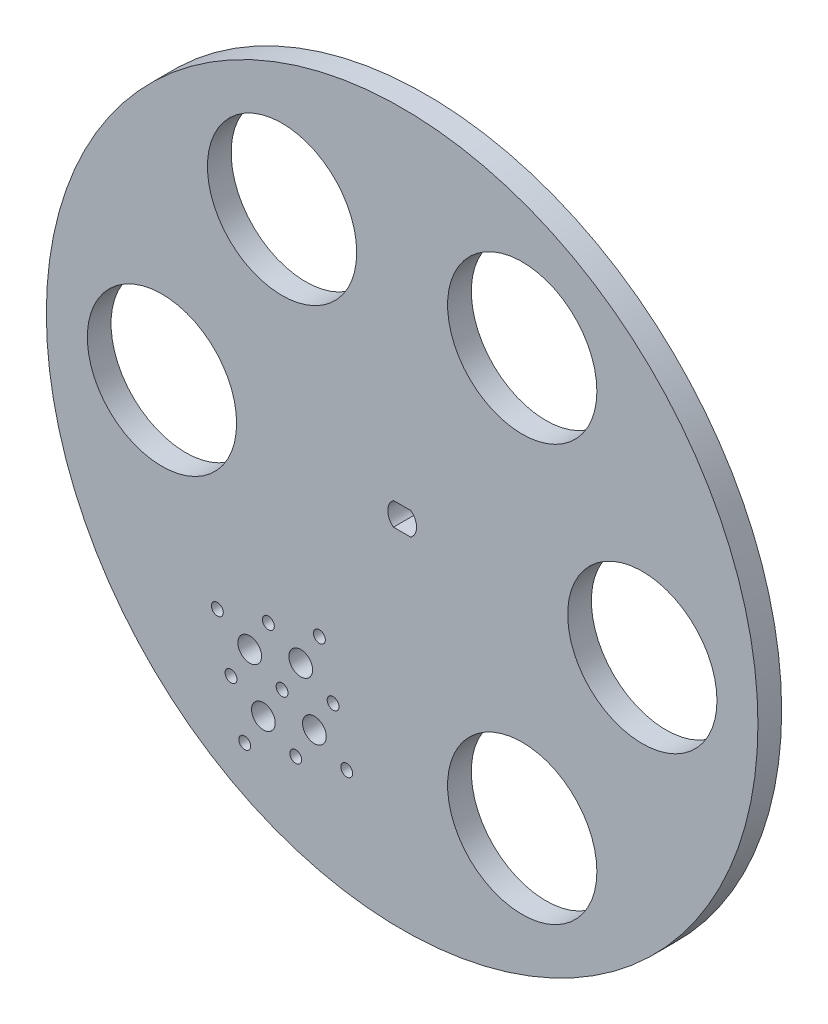
SolidWorks part; units mm, degrees
note: The reader was unsure of these and kept them because the rebuilt part matched: shared geometry of "草圖2<4>".
ref_plane "前基準面" through (0, 0, 0) normal (0, 0, 1) x (1, 0, 0)
ref_plane "上基準面" through (0, 0, 0) normal (0, 1, 0) x (1, 0, 0)
ref_plane "右基準面" through (0, 0, 0) normal (1, 0, 0) x (0, 0, -1)
sketch "草圖1" plane through (0, 0, 0) normal (0, 0, 1) x (1, 0, 0)
  line L1 (60, 0) -> (-60, 0)
  line L2 (20.25, 35.074) -> (-20.25, -35.074)
  line L3 (-20.25, 35.074) -> (20.25, -35.074)
  circle A0 centre (0, 0) radius 40.5
  circle A1 centre (0, 0) radius 60
  arc A2 (0, 40.5) -> (35.074, 20.25) centre (0, 0) cw
  arc A3 (40.5, 0) -> (20.25, -35.074) centre (0, 0) cw
  arc A4 (-40.5, 0) -> (-20.25, -35.074) centre (0, 0) ccw
  point P7 (0, 0)
  point P10 (0, 0)
  point P15 (0, 0)
  point P16 (0, 0)
  point P17 (0, 0)
  point P22 (0, 0)
  point P23 (0, 0)
  point P25 (0, 0)
  point P28 (0, 0)
  dimension "D1" = 81
  dimension "D2" = 120
sketch "草圖2" plane through (0, 0, 0) normal (0, 0, 1) x (1, 0, 0)
  line L1 (60, 0) -> (-60, 0) construction
  line L2 (20.25, 35.074) -> (-20.25, -35.074) construction
  line L9 (20.25, -35.074) -> (9.3489, -28.7803) construction
  line L47 (7.6625, -35.074) -> (20.25, -35.074) construction
  line L49 (-1.46, -1.9425) -> (1.46, -1.9425)
  line L51 (1.46, 1.9425) -> (-1.46, 1.9425)
  circle A1 centre (0, 0) radius 40.5 construction
  circle A2 centre (-40.5, 0) radius 12.5875
  circle A30 centre (-20.25, 35.074) radius 12.5875
  circle A31 centre (20.25, 35.074) radius 12.5875
  circle A32 centre (40.5, 0) radius 12.5875
  circle A33 centre (20.25, -35.074) radius 12.5875
  circle A34 centre (-20.25, -35.074) radius 1
  circle A35 centre (-17.1, -29.6181) radius 2
  circle A36 centre (-22.556, -26.4681) radius 1
  circle A37 centre (-11.644, -32.7681) radius 1
  circle A38 centre (-17.944, -43.68) radius 1
  circle A39 centre (-28.856, -37.38) radius 1
  circle A41 centre (-14.794, -38.224) radius 2
  circle A42 centre (-25.706, -31.924) radius 2
  circle A43 centre (-23.4, -40.53) radius 2
  circle A44 centre (-31.1619, -28.774) radius 1
  circle A45 centre (-13.95, -24.1621) radius 1
  circle A46 centre (-9.3381, -41.374) radius 1
  circle A47 centre (-26.55, -45.9859) radius 1
  circle A54 centre (0, 0) radius 4.5
  arc A58 (-1.46, 1.9425) -> (-1.46, -1.9425) centre (0, 0) ccw
  arc A59 (1.46, -1.9425) -> (1.46, 1.9425) centre (0, 0) ccw
  point P25 (-0.0097, 0)
  point P26 (0, 0)
  point P28 (0, 0)
  point P29 (-0.2266, 0)
  point P31 (-1.5, 0)
  point P39 (-20.25, -35.074)
  point P42 (-20.25, -35.074)
  point P50 (3.2033, -2.7559)
  point P54 (0, 0)
  point P57 (2, 0)
  point P67 (-1.5, 0)
  point P73 (1.5, 0)
  dimension "D1" = 2.92
  dimension "D3" = 2.43
  dimension "D4" = 25.175
  dimension "D5" = 25.175
  dimension "D6" = 25.175
  dimension "D7" = 25.175
  dimension "D8" = 25.175
  dimension "D2" = 2.92
extrude "填料-伸長1" add sketch "草圖1" along normal blind 4 contours A1
extrude "除料-伸長2" cut sketch "草圖2" along normal blind 4
extrude "填料-伸長2" add sketch "草圖2<4>" against normal blind 2.85 contours A54 A59 L49 A58 L51
sketch "草圖2<4>" plane through (0, 0, 0) normal (0, 0, 1) x (1, 0, 0) same geometry as "草圖2"
